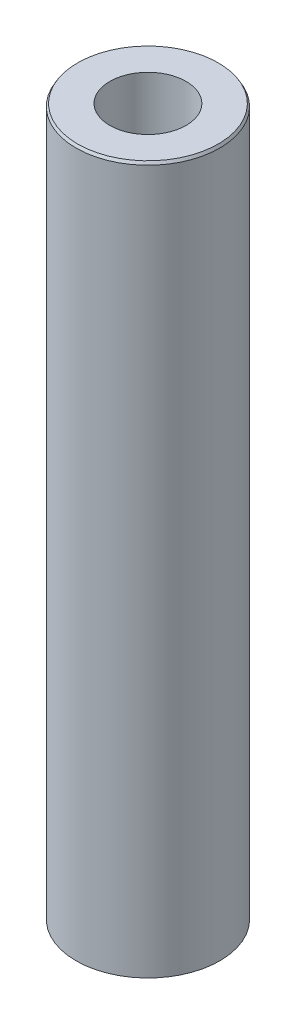
SolidWorks part; units mm, degrees
ref_plane "Front Plane" through (0, 0, 0) normal (0, 0, 1) x (1, 0, 0)
ref_plane "Top Plane" through (0, 0, 0) normal (0, 1, 0) x (1, 0, 0)
ref_plane "Right Plane" through (0, 0, 0) normal (1, 0, 0) x (0, 0, -1)
sketch "Sketch1" plane through (0, 0, 0) normal (0, 1, 0) x (1, 0, 0)
  circle A0 centre (0, 0) radius 47.5
  dimension "SHAFT_OD" = 95
extrude "Boss-Extrude1" add sketch "Sketch1" along normal blind 467.8895
sketch "Sketch2" plane through (0, 0, 0) normal (0, 1, 0) x (1, 0, 0)
  circle A0 centre (0, 0) radius 25.2132
  dimension "BORE_D" = 50.4265
extrude "Cut-Extrude1" cut sketch "Sketch2" along normal through all
chamfer "Chamfer1" distance 1.7983 angle 30 2 edges at (0, 467.8895, 47.5) (0, 0, 47.5) first distance on face at (0, 467.8895, 47.5) first distance on face at (0, 0, 25.2132)
